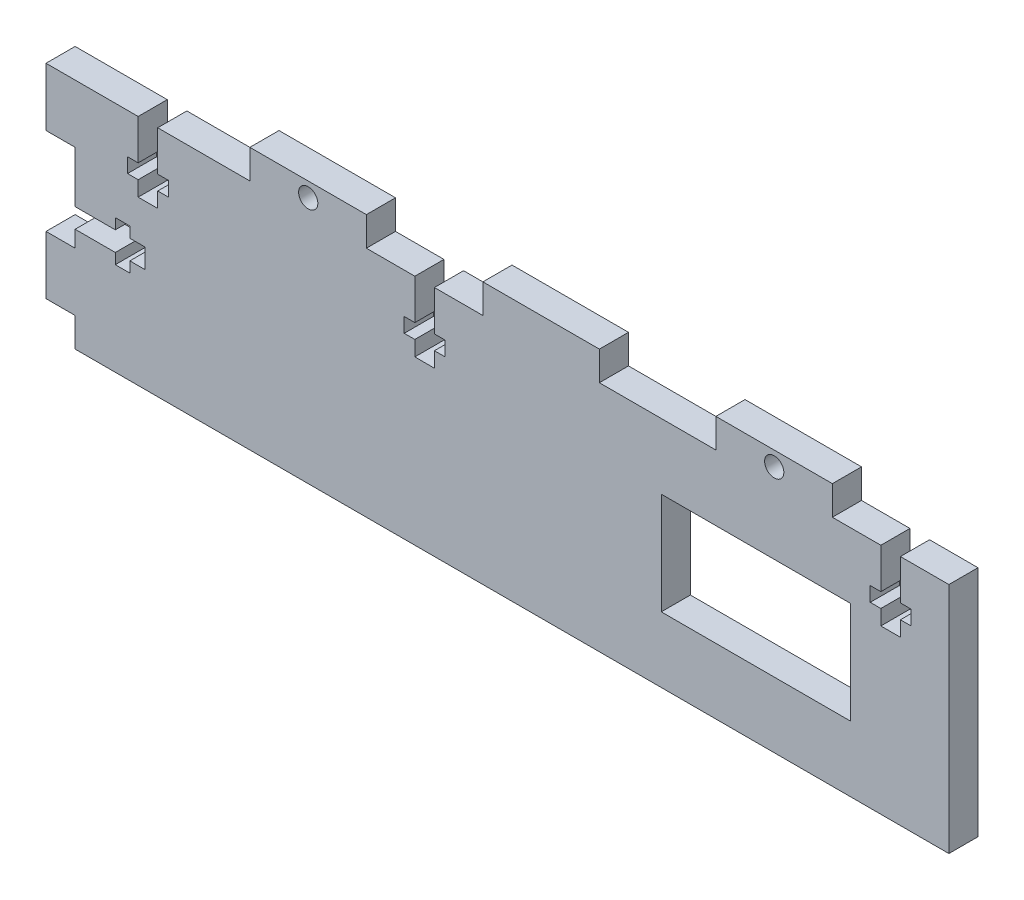
SolidWorks part; units mm, degrees
ref_plane "Front Plane" through (0, 0, 0) normal (0, 0, 1) x (1, 0, 0)
ref_plane "Top Plane" through (0, 0, 0) normal (0, 1, 0) x (1, 0, 0)
ref_plane "Right Plane" through (0, 0, 0) normal (1, 0, 0) x (0, 0, -1)
sketch "Sketch1" plane through (0, 0, 0) normal (0, 0, 1) x (1, 0, 0)
  line L0 (69.2576, 0) -> (-63.1151, 0) construction
  line L1 (42.067, 25.4) -> (-148.433, 25.4)
  line L2 (42.067, 25.4) -> (42.067, -25.4)
  line L3 (42.067, -25.4) -> (-148.433, -25.4)
  line L4 (-148.433, 25.4) -> (-148.433, -25.4)
  line L7 (25.98, 9.3599) -> (20.1295, 9.3599) construction
  line L8 (20.1295, -9.3599) -> (25.98, -9.3599) construction
  line L9 (-148.433, -69.85) -> (-148.433, 49.2353) construction
  line L10 (27.25, 6.27) -> (27.25, 8.0899) construction
  dimension "D1" = 50.8
  dimension "D2" = 14.817
extrude "Boss-Extrude1" add sketch "Sketch1" along normal blind 6.35
sketch "Sketch2" plane through (0, 0, 6.35) normal (0, 0, 1) x (1, 0, 0)
  line L0 (-43.1818, 0) -> (35.1848, 0) construction
  line L1 (-20.6375, 11.1125) -> (20.6375, 11.1125)
  line L2 (-20.6375, 11.1125) -> (-20.6375, -11.1125)
  line L3 (-20.6375, -11.1125) -> (20.6375, -11.1125)
  line L4 (20.6375, 11.1125) -> (20.6375, -11.1125)
  line L5 (-19.6295, 10.033) -> (19.6295, 10.033) construction
  line L6 (19.6295, -10.033) -> (-19.6295, -10.033) construction
  line L7 (0, 18.8234) -> (0, -13.1279) construction
  line L8 (-20.1295, -9.533) -> (-20.1295, 9.533) construction
  line L9 (20.1295, 9.533) -> (20.1295, -9.533) construction
  dimension "D1" = 22.225
  dimension "D2" = 41.275
extrude "Cut-Extrude1" cut sketch "Sketch2" against normal through all
sketch "Sketch3" plane through (0, 25.4, 0) normal (0, 1, 0) x (1, 0, 0)
  line L0 (16.667, 0) -> (16.667, -6.35)
  line L1 (42.067, 0) -> (-148.433, 0) construction
  line L2 (42.067, -6.35) -> (-148.433, -6.35) construction
  line L3 (16.667, -6.35) -> (-8.733, -6.35)
  line L4 (-8.733, -6.35) -> (-8.733, 0)
  line L5 (-8.733, 0) -> (16.667, 0)
  dimension "D1" = 25.4
  dimension "D2" = 25.4
extrude "Boss-Extrude2" add sketch "Sketch3" along normal blind 6.35
pattern_linear "LPattern1" count 3 spacing 50.8 along (-1, 0, 0) of "Boss-Extrude2"
sketch "Sketch4" plane through (-148.433, 0, 0) normal (-1, 0, 0) x (0, 0, 1)
  line L0 (6.35, 25.4) -> (6.35, 12.7)
  line L1 (6.35, 25.4) -> (6.35, -25.4) construction
  line L2 (6.35, 12.7) -> (0, 12.7)
  line L3 (0, 25.4) -> (0, -25.4) construction
  line L4 (0, 12.7) -> (0, 25.4)
  line L5 (0, 25.4) -> (6.35, 25.4)
  dimension "D1" = 12.7
extrude "Boss-Extrude3" add sketch "Sketch4" along normal blind 6.35
pattern_linear "LPattern2" count 2 spacing 31.75 along (0, -1, 0) of "Boss-Extrude3"
sketch "Sketch5" plane through (0, 0, 6.35) normal (0, 0, 1) x (1, 0, 0)
  line L1 (29.367, 25.4) -> (29.367, -8.4837) construction
  line L2 (42.067, 25.4) -> (16.667, 25.4) construction
  line L3 (-72.233, 25.4) -> (-72.233, 3.5007) construction
  line L4 (-59.533, 25.4) -> (-84.933, 25.4) construction
  line L5 (-132.558, 25.4) -> (-132.558, 4.6588) construction
  line L6 (-110.333, 25.4) -> (-154.783, 25.4) construction
  line B0 (31.5006, 25.4) -> (27.2334, 25.4)
  line B1 (27.2334, 13.462) -> (24.922, 13.462)
  line B2 (24.922, 13.462) -> (24.922, 16.637)
  line B3 (24.922, 16.637) -> (27.2334, 16.637)
  line B4 (27.2334, 16.637) -> (27.2334, 25.4)
  line B5 (27.2334, 13.462) -> (27.2334, 10.16)
  line B6 (27.2334, 10.16) -> (31.5006, 10.16)
  line B7 (31.5006, 13.462) -> (31.5006, 10.16)
  line B8 (31.5006, 16.637) -> (31.5006, 25.4)
  line B9 (33.812, 16.637) -> (31.5006, 16.637)
  line B10 (33.812, 13.462) -> (33.812, 16.637)
  line B11 (31.5006, 13.462) -> (33.812, 13.462)
  line B12 (-70.0994, 25.4) -> (-74.3666, 25.4)
  line B13 (-74.3666, 13.462) -> (-76.678, 13.462)
  line B14 (-76.678, 13.462) -> (-76.678, 16.637)
  line B15 (-76.678, 16.637) -> (-74.3666, 16.637)
  line B16 (-74.3666, 16.637) -> (-74.3666, 25.4)
  line B17 (-74.3666, 13.462) -> (-74.3666, 10.16)
  line B18 (-74.3666, 10.16) -> (-70.0994, 10.16)
  line B19 (-70.0994, 13.462) -> (-70.0994, 10.16)
  line B20 (-70.0994, 16.637) -> (-70.0994, 25.4)
  line B21 (-67.788, 16.637) -> (-70.0994, 16.637)
  line B22 (-67.788, 13.462) -> (-67.788, 16.637)
  line B23 (-70.0994, 13.462) -> (-67.788, 13.462)
  line B24 (-130.4244, 25.4) -> (-134.6916, 25.4)
  line B25 (-134.6916, 13.462) -> (-137.003, 13.462)
  line B26 (-137.003, 13.462) -> (-137.003, 16.637)
  line B27 (-137.003, 16.637) -> (-134.6916, 16.637)
  line B28 (-134.6916, 16.637) -> (-134.6916, 25.4)
  line B29 (-134.6916, 13.462) -> (-134.6916, 10.16)
  line B30 (-134.6916, 10.16) -> (-130.4244, 10.16)
  line B31 (-130.4244, 13.462) -> (-130.4244, 10.16)
  line B32 (-130.4244, 16.637) -> (-130.4244, 25.4)
  line B33 (-128.113, 16.637) -> (-130.4244, 16.637)
  line B34 (-128.113, 13.462) -> (-128.113, 16.637)
  line B35 (-130.4244, 13.462) -> (-128.113, 13.462)
sketch_block_instance "TSlot-1"
sketch_block "TSlot" parameters "D1"=3.302, "D2"=3.175
sketch_block_instance "TSlot-4"
sketch_block_instance "TSlot-5"
extrude "Cut-Extrude2" cut sketch "Sketch5" against normal blind 6.35
sketch "Sketch6" plane through (0, 0, 0) normal (0, 0, -1) x (-1, 0, 0)
  line L0 (-1.854, 31.75) -> (-6.1212, 25.4) construction
  line L1 (-16.667, 31.75) -> (8.733, 31.75) construction
  line L2 (-1.854, 31.75) -> (-1.854, 25.4) construction
  line L3 (-6.1212, 31.75) -> (-1.854, 25.4) construction
  line L4 (-6.1212, 25.4) -> (-6.1212, 31.75) construction
  line L5 (99.746, 31.75) -> (95.4788, 25.4) construction
  line L6 (84.933, 31.75) -> (110.333, 31.75) construction
  line L7 (99.746, 31.75) -> (99.746, 25.4) construction
  line L8 (95.4788, 31.75) -> (99.746, 25.4) construction
  line L9 (95.4788, 25.4) -> (95.4788, 31.75) construction
  circle A0 centre (-3.9876, 28.575) radius 2.0955
  circle A1 centre (97.6124, 28.575) radius 2.0955
  dimension "D1" = 4.191
extrude "Cut-Extrude3" cut sketch "Sketch6" against normal through all
sketch "Sketch7" plane through (0, 0, 6.35) normal (0, 0, 1) x (1, 0, 0)
  line L1 (-148.433, 12.7) -> (-148.433, -6.35) construction
  line L2 (-134.6916, 10.16) -> (-130.4244, 10.16) construction
  line L3 (-134.6916, 10.16) -> (-130.4244, 10.16) construction
  point P5 (-132.558, 10.16)
  line B0 (-148.433, 1.4986) -> (-148.433, -2.7686)
  line B1 (-136.495, -2.7686) -> (-136.495, -5.08)
  line B2 (-136.495, -5.08) -> (-139.67, -5.08)
  line B3 (-139.67, -5.08) -> (-139.67, -2.7686)
  line B4 (-139.67, -2.7686) -> (-148.433, -2.7686)
  line B5 (-136.495, -2.7686) -> (-133.193, -2.7686)
  line B6 (-133.193, -2.7686) -> (-133.193, 1.4986)
  line B7 (-136.495, 1.4986) -> (-133.193, 1.4986)
  line B8 (-139.67, 1.4986) -> (-148.433, 1.4986)
  line B9 (-139.67, 3.81) -> (-139.67, 1.4986)
  line B10 (-136.495, 3.81) -> (-139.67, 3.81)
  line B11 (-136.495, 1.4986) -> (-136.495, 3.81)
  dimension "D1" = 6.35
sketch_block_instance "TSlot-6"
extrude "Cut-Extrude4" cut sketch "Sketch7" against normal through all
